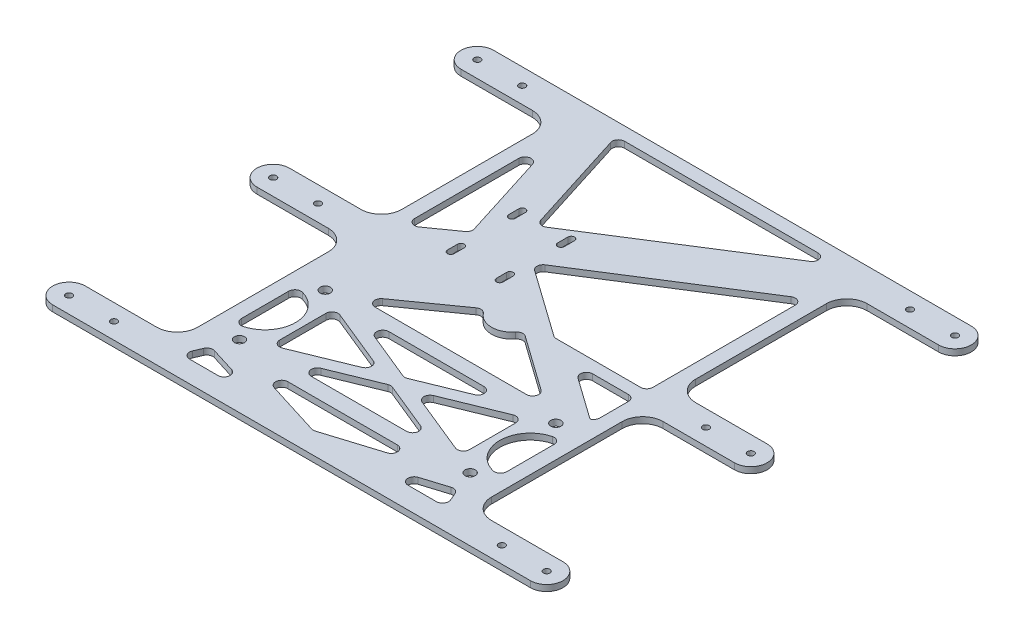
SolidWorks part; units mm, degrees
material "Hexcel AS4C (3000 丝)"
ref_plane "前视基准面" through (0, 0, 0) normal (0, 0, 1) x (1, 0, 0)
ref_plane "上视基准面" through (0, 0, 0) normal (0, 1, 0) x (1, 0, 0)
ref_plane "右视基准面" through (0, 0, 0) normal (1, 0, 0) x (0, 0, -1)
sketch "草图1" plane through (0, 0, 0) normal (0, 1, 0) x (1, 0, 0)
  line L0 (0, -350.4727) -> (0, 17173.1623) construction
  line L1 (-350.4727, 0) -> (17173.1623, 0) construction
  line L2 (-95, -1000) -> (-95, 49000) construction
  line L3 (-117, 0) -> (-95, 0) construction
  line L4 (-117, 8) -> (-95, 8)
  line L5 (-117, -8) -> (-95, -8)
  line L6 (-117, 100) -> (-95, 100) construction
  line L7 (-117, 108) -> (-95, 108)
  line L8 (-117, 92) -> (-95, 92)
  line L9 (-117, -100) -> (-95, -100) construction
  line L10 (-117, -108) -> (-95, -108)
  line L11 (-117, -92) -> (-95, -92)
  line L12 (117, 100) -> (95, 100) construction
  line L13 (117, 108) -> (95, 108)
  line L14 (117, 92) -> (95, 92)
  line L15 (117, 0) -> (95, 0) construction
  line L16 (117, 8) -> (95, 8)
  line L17 (117, -8) -> (95, -8)
  line L18 (117, -100) -> (95, -100) construction
  line L19 (117, -108) -> (95, -108)
  line L20 (117, -92) -> (95, -92)
  line L21 (-95, 8) -> (95, 8)
  line L22 (-95, 108) -> (95, 108)
  line L23 (-95, 92) -> (95, 92)
  line L24 (-95, -8) -> (95, -8)
  line L25 (-95, -108) -> (95, -108)
  line L26 (-95, -92) -> (95, -92)
  line L28 (-72, -92) -> (72, -92)
  line L29 (-72, -92) -> (-72, 92)
  line L30 (-72, 92) -> (72, 92)
  line L31 (72, -92) -> (72, 92)
  line L32 (-72, -92) -> (72, 92) construction
  line L33 (-72, 92) -> (72, -92) construction
  circle A0 centre (-95, 0) radius 1.6
  circle A2 centre (-95, 100) radius 1.6
  circle A3 centre (-95, -100) radius 1.6
  circle A4 centre (95, -100) radius 1.6
  circle A5 centre (95, 100) radius 1.6
  circle A6 centre (95, 0) radius 1.6
  circle A7 centre (-117, 0) radius 1.6
  circle A8 centre (-117, 100) radius 1.6
  circle A9 centre (-117, -100) radius 1.6
  circle A10 centre (117, -100) radius 1.6
  circle A11 centre (117, 100) radius 1.6
  circle A12 centre (117, 0) radius 1.6
  arc A13 (-117, 8) -> (-117, -8) centre (-117, 0) ccw
  arc A14 (-95, -8) -> (-95, 8) centre (-95, 0) ccw
  arc A15 (-117, 108) -> (-117, 92) centre (-117, 100) ccw
  arc A16 (-95, 92) -> (-95, 108) centre (-95, 100) ccw
  arc A17 (-117, -108) -> (-117, -92) centre (-117, -100) cw
  arc A18 (-95, -92) -> (-95, -108) centre (-95, -100) cw
  arc A19 (117, 108) -> (117, 92) centre (117, 100) cw
  arc A20 (95, 92) -> (95, 108) centre (95, 100) cw
  arc A21 (117, 8) -> (117, -8) centre (117, 0) cw
  arc A22 (95, -8) -> (95, 8) centre (95, 0) cw
  arc A23 (117, -108) -> (117, -92) centre (117, -100) ccw
  arc A24 (95, -92) -> (95, -108) centre (95, -100) ccw
  point P31 (-106, 0)
  point P36 (-106, 100)
  point P41 (-106, -100)
  point P46 (106, 100)
  point P51 (106, 0)
  point P56 (106, -100)
  point P73 (0, 0)
  dimension "D1" = 95
  dimension "D2" = 3.2
  dimension "D3" = 100
  dimension "D6" = 8
  dimension "D7" = 8
  dimension "D5" = 22
  dimension "D8" = 72
  dimension "D4" = 2
extrude "凸台-拉伸1" add sketch "草图1" along normal blind 3 contours L24 L31 L21 L29 | L26 L31 L24 L29 | L21 L31 L23 L29 | A14 L24 L29 L21 | L5 A14 L4 A13 A7 A0 | A18 L11 A17 L10 A3 A9 | A24 L26 A18 L25 | L20 A24 L19 A23 A10 A4 | A20 L14 A19 L13 A5 A11 | A22 L17 A21 L16 A6 A12 | L24 A22 L21 L31 | L23 A20 L22 A16 | L8 A16 L7 A15 A8 A2 region at (-106, 0, 0) region at (-80.4538, 0, 0) region at (0, 0, -50) region at (0, 0, 0) region at (80.4538, 0, 0) region at (0, 0, 50) region at (0, 0, -100) region at (106, 0, 0) region at (0, 0, 100) region at (-106, 0, -100) region at (106, 0, -100) region at (-106, 0, 100) region at (106, 0, 100)
fillet "圆角1" radius 10 8 edges at (72, 1.5, -92) (72, 1.5, -8) (72, 1.5, 8) (72, 1.5, 92) (-72, 1.5, 92) (-72, 1.5, 8) (-72, 1.5, -8) (-72, 1.5, -92)
sketch "草图2" plane through (0, 3, 0) normal (0, 1, 0) x (1, 0, 0)
  line L0 (-1000, 0) -> (49000, 0) construction
  line L1 (-969.2325, 27) -> (49030.7675, 27) construction
  line L2 (-42, 42) -> (-42, 12) construction
  line L3 (-42, 47) -> (-42, 17) construction
  line L4 (-42, 12) -> (-42, 17) construction
  line L5 (-43.6, 17) -> (-43.6, 12)
  line L6 (-40.4, 17) -> (-40.4, 12)
  line L7 (-19.6, 17) -> (-19.6, 12)
  line L8 (-16.4, 17) -> (-16.4, 12)
  line L9 (-19.6, 47) -> (-19.6, 42)
  line L10 (-16.4, 47) -> (-16.4, 42)
  line L11 (-43.6, 47) -> (-43.6, 42)
  line L12 (-40.4, 47) -> (-40.4, 42)
  circle A0 centre (-42, 12) radius 1.6
  circle A1 centre (-18, 12) radius 1.6
  circle A2 centre (-18, 42) radius 1.6
  circle A3 centre (-42, 42) radius 1.6
  circle A4 centre (-42, 17) radius 1.6
  circle A5 centre (-18, 17) radius 1.6
  circle A6 centre (-18, 47) radius 1.6
  circle A7 centre (-42, 47) radius 1.6
  point P5 (-42, 27)
  dimension "D1" = 3.2
  dimension "D4" = 30
  dimension "D5" = 24
  dimension "D7" = 42
  dimension "D6" = 27
  dimension "D9" = 5
  dimension "D2" = 2
  dimension "D3" = 2
  dimension "D8" = 2
  dimension "D10" = 2
  dimension "D11" = 2
extrude "切除-拉伸1" cut sketch "草图2" against normal through all contours A7 L11 A3 L12 | A7 | A3 | A2 | A6 L9 A2 L10 | A6 | A5 | A5 L7 A1 L8 | A1 | A0 | A4 L5 A0 L6 | A4 region at (-42, 3, -14.5) region at (-42, 3, -17) region at (-42, 3, -12) region at (-18, 3, -14.5) region at (-18, 3, -17) region at (-18, 3, -12) region at (-18, 3, -44.5) region at (-18, 3, -47) region at (-18, 3, -42) region at (-42, 3, -44.5) region at (-42, 3, -47) region at (-42, 3, -42)
sketch "草图4" plane through (0, 3, 0) normal (0, 1, 0) x (1, 0, 0)
  line L0 (-56.5, -35) -> (56.5, -35) construction
  line L1 (0, 0) -> (0, -35) construction
  circle A0 centre (-56.5, -35) radius 2.5
  circle A1 centre (56.5, -35) radius 2.5
  circle A2 centre (56.5, -77) radius 2.5
  circle A3 centre (-56.5, -77) radius 2.5
  dimension "D1" = 5
  dimension "D4" = 42
  dimension "D5" = 113
  dimension "D6" = 35
  dimension "D2" = 2
  dimension "D3" = 2
extrude "切除-拉伸2" cut sketch "草图4" against normal through all
sketch "草图5" plane through (0, 3, 0) normal (0, 1, 0) x (1, 0, 0)
  line L0 (0, -1000) -> (0, 49000) construction
  line L1 (-65, 97.5) -> (65, 97.5)
  line L2 (-65, 97.5) -> (-65, -97.5)
  line L3 (-65, -97.5) -> (65, -97.5)
  line L4 (65, 97.5) -> (65, -97.5)
  line L5 (-65, -25) -> (-46.5, -25)
  line L6 (-65, -25) -> (-65, -87)
  line L7 (-65, -87) -> (-46.5, -87)
  line L8 (-46.5, -25) -> (-46.5, -87)
  line L9 (-1000, 0) -> (49000, 0) construction
  line L10 (65, -87) -> (46.5, -87)
  line L11 (46.5, -25) -> (46.5, -87)
  line L12 (65, -25) -> (46.5, -25)
  line L13 (65, -25) -> (65, -87)
  line L14 (-65, 16.3548) -> (-50, 27)
  line L15 (-50, 50) -> (-10, 50)
  line L16 (-50, 50) -> (-50, 4)
  line L17 (-50, 4) -> (-10, 4)
  line L18 (-10, 50) -> (-10, 4)
  line L19 (-50, 27) -> (-65, 74.5)
  line L20 (-45, 97.5) -> (-30, 50)
  line L21 (-30, 50) -> (45, 97.5)
  line L22 (65, 74.5) -> (-10, 27)
  line L23 (-10, 27) -> (65, -26.2258)
  line L24 (0, 3) -> (46.5, -30)
  line L25 (0, 3) -> (-46.5, -30)
  line L26 (-46.5, -83) -> (46.5, -83)
  line L27 (-46.5, -30) -> (46.5, -30)
  line L28 (-46.5, -37) -> (46.5, -75) construction
  line L29 (46.5, -37) -> (-46.5, -75) construction
  line L30 (-46.5, -75) -> (46.5, -75)
  line L31 (46.5, -37) -> (-46.5, -37)
  line L32 (-46.5, -83) -> (0, -97.5)
  line L33 (0, -97.5) -> (46.5, -83)
  line L34 (-1000, -56) -> (49000, -56) construction
  line L35 (-38.5686, -37) -> (46.5, -71.7592)
  line L36 (-38.5686, -75) -> (46.5, -40.2408)
  line L37 (38.5686, -75) -> (-46.5, -40.2408)
  line L38 (38.5686, -37) -> (-46.5, -71.7592)
  line L39 (-60.546, -87) -> (-26.8736, -97.5)
  line L40 (60.546, -87) -> (26.8736, -97.5)
  line L41 (60.546, -87) -> (65, -97.5)
  line L42 (-60.546, -87) -> (-65, -97.5)
  line L43 (21, 5) -> (65, 5)
  line L44 (35.0909, -5) -> (65, -5)
  circle A0 centre (-56.5, -77) radius 2.5 construction
  circle A1 centre (-56.5, -35) radius 2.5 construction
  circle A2 centre (-18, 12) radius 1.6 construction
  circle A3 centre (-42, 12) radius 1.6 construction
  circle A4 centre (-18, 42) radius 1.6 construction
  circle A5 centre (56.5, -35) radius 2.5 construction
  circle A6 centre (56.5, -77) radius 2.5 construction
  circle A7 centre (65, -56) radius 15
  circle A8 centre (-65, -56) radius 15
  point P9 (0, 97.5)
  point P13 (65, 0)
  point P59 (0, -56)
  dimension "D3" = 10
  dimension "D5" = 10
  dimension "D7" = 8
  dimension "D8" = 8
  dimension "D9" = 8
  dimension "D22" = 30
  dimension "D1" = 130
  dimension "D2" = 195
  dimension "D4" = 10
  dimension "D6" = 8
  dimension "D10" = 5
  dimension "D11" = 5
  dimension "D12" = 20
  dimension "D13" = 20
  dimension "D14" = 2
  dimension "D15" = 2
  dimension "D16" = 8
  dimension "D17" = 3
  dimension "D18" = 8
  dimension "D19" = 5
  dimension "D20" = 3
  dimension "D21" = 5
extrude "切除-拉伸4" cut sketch "草图5" against normal blind 10 contours L32 L33 L26 | L30 L37 L36 | L38 L37 L8 | L38 L31 L35 | L36 L35 L11 | L25 L27 L24 | L22 L23 L4 | L14 L19 L2 | L20 L21 L1 | L39 L7 L2 L3 | L10 L40 L3 L4 | L44 L23 L12 L4 | A8 L6 | L4 A7 region at (-10, 3, -81.6667) region at (-60, 3, -39.2849) region at (37.7029, 3, -31.8716) region at (-58.6338, 3, 56) region at (0, 3, 19) region at (54.9989, 3, 12.0307) region at (-50.8065, 3, 94) region at (-33.6438, 3, 56) region at (0, 3, 42.2531) region at (33.6438, 3, 56) region at (58.6338, 3, 56) region at (0, 3, 87.8333) region at (0, 3, 69.7469) region at (50.8065, 3, 94)
sketch "草图6" plane through (0, 3, 0) normal (0, 1, 0) x (1, 0, 0)
  circle A0 centre (0, 0) radius 10
  dimension "D1" = 20
extrude "凸台-拉伸2" add sketch "草图6" against normal through all
sketch "草图8" plane through (0, 3, 0) normal (0, 1, 0) x (1, 0, 0)
  line L0 (-69, 8.6112) -> (-45.3079, 25.4249)
  line L1 (-50, 50) -> (-10, 50)
  line L2 (-50, 50) -> (-50, -3.6164)
  line L3 (-9.3232, -3.6164) -> (-46.5, -30)
  line L4 (46.5, -30) -> (9.3232, -3.6164)
  line L5 (-46.5, -30) -> (46.5, -30)
  line L6 (-9.3232, -3.6164) -> (-46.5, -30)
  line L7 (46.5, -30) -> (9.3232, -3.6164)
  line L8 (-46.5, -30) -> (46.5, -30)
  line L9 (-45, 97.5) -> (-30, 50)
  line L10 (-10, 27) -> (21, 5)
  line L11 (65, 74.5) -> (-10, 27)
  line L12 (65, 5) -> (65, 74.5)
  line L13 (21, 5) -> (65, 5)
  line L14 (-10, 27) -> (21, 5)
  line L15 (65, 74.5) -> (-10, 27)
  line L16 (65, 5) -> (65, 74.5)
  line L17 (21, 5) -> (65, 5)
  line L18 (45, 97.5) -> (-45, 97.5)
  line L19 (-30, 50) -> (45, 97.5)
  line L20 (-45, 97.5) -> (-30, 50)
  line L21 (45, 97.5) -> (-45, 97.5)
  line L22 (-30, 50) -> (45, 97.5)
  line L23 (-65, 16.3548) -> (-50, 27)
  line L24 (-65, 74.5) -> (-65, 16.3548)
  line L25 (-50, 27) -> (-65, 74.5)
  line L26 (-65, 16.3548) -> (-50, 27)
  line L27 (-65, 74.5) -> (-65, 16.3548)
  line L28 (-50, 27) -> (-65, 74.5)
  line L29 (-50, -3.6164) -> (-10, -3.6164)
  line L30 (-10, 50) -> (-10, -3.6164)
  line L31 (-45.3079, 25.4249) -> (-69, 100.4499)
  line L32 (-69, 100.4499) -> (-69, 8.6112)
  line L33 (-50.4579, 101.5) -> (-32.2496, 43.8405)
  line L34 (-32.2496, 43.8405) -> (58.7917, 101.5)
  line L35 (58.7917, 101.5) -> (-50.4579, 101.5)
  line L36 (-17.1777, 27.1889) -> (19.7249, 1)
  line L37 (19.7249, 1) -> (69, 1)
  line L38 (69, 1) -> (69, 81.7681)
  line L39 (69, 81.7681) -> (-17.1777, 27.1889)
  line L40 (-46.5, -3.6164) -> (-46.5, -30)
  line L41 (-10, -3.6164) -> (-9.3232, -3.6164)
  line L42 (-65, -988.9677) -> (-65, 49011.0323)
  line L43 (65, -995) -> (65, 49005)
  arc A1 (-9.3232, -3.6164) -> (9.3232, -3.6164) centre (0, 0) ccw
  arc A2 (-9.3232, -3.6164) -> (9.3232, -3.6164) centre (0, 0) ccw
  dimension "D1" = 0
  dimension "D2" = 0
  dimension "D3" = 0
  dimension "D4" = 0
  dimension "D5" = 4
extrude "切除-拉伸6" cut sketch "草图8" against normal through all contours L42 L28 L2 L31 | L42 L0 L2 L26 | L0 L31 L2 | L26 L28 L27 | L34 L35 L33 L1 L20 L21 L22 | L33 L34 L1 | L15 L43 L39 L30 | L30 L39 L36 | L37 L43 L17 L14 L30 L36 region at (-57.5, 3, -19.225) region at (-48.436, 3, -29.2678) region at (-60, 3, -39.2849) region at (-57.5, 3, -57.3916) region at (-41.1746, 3, -76.1137) region at (-29.6561, 3, -47.9468) region at (-12.3926, 3, -27.0062) region at (-9.2062, 3, -24.5475) region at (27.5, 3, -53.1174)
fillet "圆角2" radius 3 43 edges at (0, 1.5, 52.7592) (-38.5686, 1.5, 37) (38.5686, 1.5, 37) (-46.5, 1.5, 71.7592) (-46.5, 1.5, 40.2408) (-7.9314, 1.5, 56) (46.5, 1.5, 30) (-46.5, 1.5, 30) (-9.3232, 1.5, 3.6164) (9.3232, 1.5, 3.6164) (65, 1.5, 97.5) (26.8736, 1.5, 97.5) (60.546, 1.5, 87) (46.5, 1.5, 83) (0, 1.5, 97.5) (-46.5, 1.5, 83) (65, 1.5, 5) (65, 1.5, 25) (63.2727, 1.5, 25) (35.0909, 1.5, 5) (-26.8736, 1.5, 97.5) (-65, 1.5, 97.5) (-60.546, 1.5, 87) (0, 1.5, 59.2408) (38.5686, 1.5, 75) (-38.5686, 1.5, 75) (46.5, 1.5, 40.2408) (46.5, 1.5, 71.7592) (7.9314, 1.5, 56) (-50.4579, 1.5, -101.5) (58.7917, 1.5, -101.5) (-32.2496, 1.5, -43.8405) (-45.3079, 1.5, -25.4249) (19.7249, 1.5, -1) (-17.1777, 1.5, -27.1889) (65, 1.5, 71) (65, 1.5, 41) (-65, 1.5, 71) (-65, 1.5, 41) (-65, 1.5, -87.7832) (-65, 1.5, -11.4499) (65, 1.5, -1) (65, 1.5, -79.2347)
